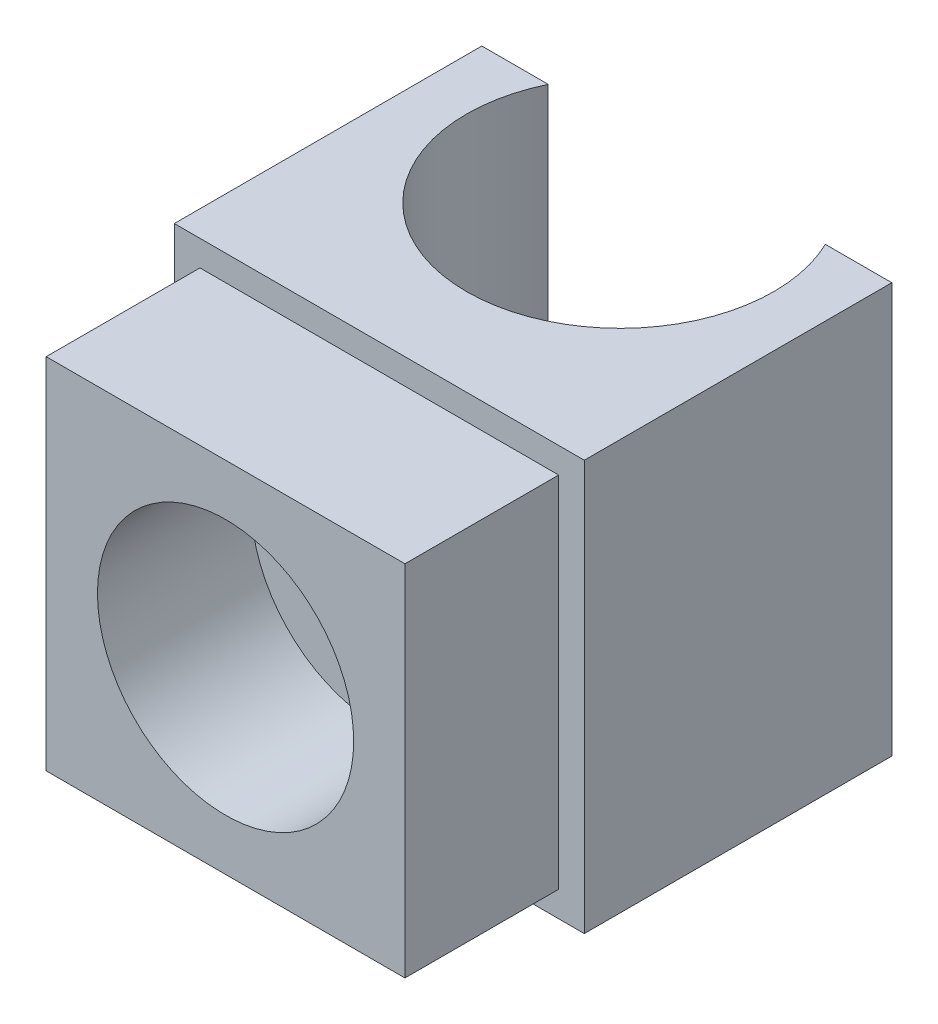
SolidWorks part; units mm, degrees
material "Aleación 1060"
ref_plane "Alzado" through (0, 0, 0) normal (0, 0, 1) x (1, 0, 0)
ref_plane "Planta" through (0, 0, 0) normal (0, 1, 0) x (1, 0, 0)
ref_plane "Vista lateral" through (0, 0, 0) normal (1, 0, 0) x (0, 0, -1)
sketch "Croquis1" plane through (0, 0, 0) normal (0, 1, 0) x (1, 0, 0)
  line L0 (0, 0) -> (0, -30) construction
  line L1 (-40, 13) -> (-27.037, 13)
  line L2 (-40, 13) -> (-40, -47)
  line L3 (-40, -47) -> (40, -47)
  line L4 (40, 13) -> (40, -47)
  line L5 (27.037, 13) -> (40, 13)
  arc A0 (-27.037, 13) -> (27.037, 13) centre (0, 0) ccw
  circle A1 centre (0, 0) radius 30 construction
  dimension "D1" = 60
  dimension "D2" = 40
  dimension "D3" = 40
  dimension "D4" = 13
  dimension "D5" = 60
extrude "Saliente-Extruir1" add sketch "Croquis1" along normal blind 40 and the other way blind 40
sketch "Croquis2" plane through (0, 0, 47) normal (0, 0, 1) x (1, 0, 0)
  line L0 (0, -40) -> (0, 40) construction
  line L1 (-40, -40) -> (40, -40) construction
  line L2 (-40, 40) -> (40, 40) construction
  line L4 (-35, -35) -> (35, -35)
  line L5 (-35, -35) -> (-35, 35)
  line L6 (-35, 35) -> (35, 35)
  line L7 (35, -35) -> (35, 35)
  line L8 (-35, -35) -> (35, 35) construction
  line L9 (-35, 35) -> (35, -35) construction
  point P6 (0, 0)
  dimension "D1" = 70
  dimension "D2" = 70
extrude "Saliente-Extruir2" add sketch "Croquis2" along normal blind 30
sketch "Croquis3" plane through (0, 0, 77) normal (0, 0, 1) x (1, 0, 0)
  circle A0 centre (0, 0) radius 25
  dimension "D1" = 50
extrude "Cortar-Extruir1" cut sketch "Croquis3" against normal blind 30
